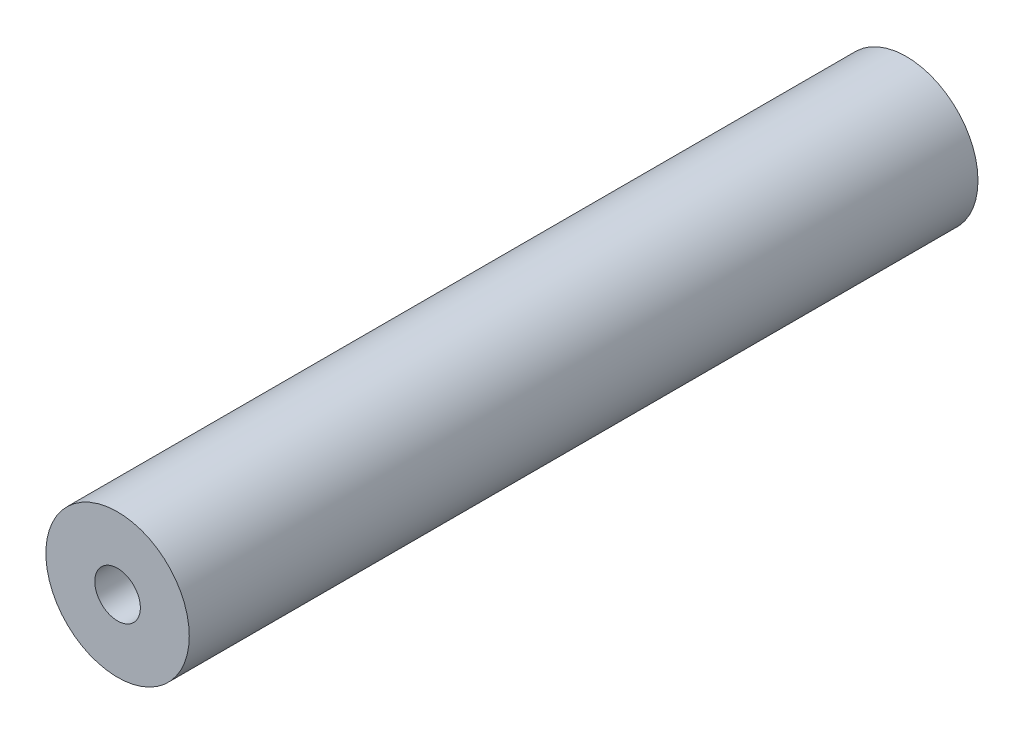
SolidWorks part; units mm, degrees
ref_plane "Front Plane" through (0, 0, 0) normal (0, 0, 1) x (1, 0, 0)
ref_plane "Top Plane" through (0, 0, 0) normal (0, 1, 0) x (1, 0, 0)
ref_plane "Right Plane" through (0, 0, 0) normal (1, 0, 0) x (0, 0, -1)
sketch "Sketch1" plane through (0, 0, 0) normal (0, 0, 1) x (1, 0, 0)
  circle A1 centre (0, 0) radius 6.35
  circle A2 centre (0, 0) radius 2.0193
  dimension "D2" = 12.7
  dimension "D3" = 4.0386
extrude "Boss-Extrude1" add sketch "Sketch1" along normal mid plane 69.85 contours A1 A2 region at (-6.1704, 0, 0)
